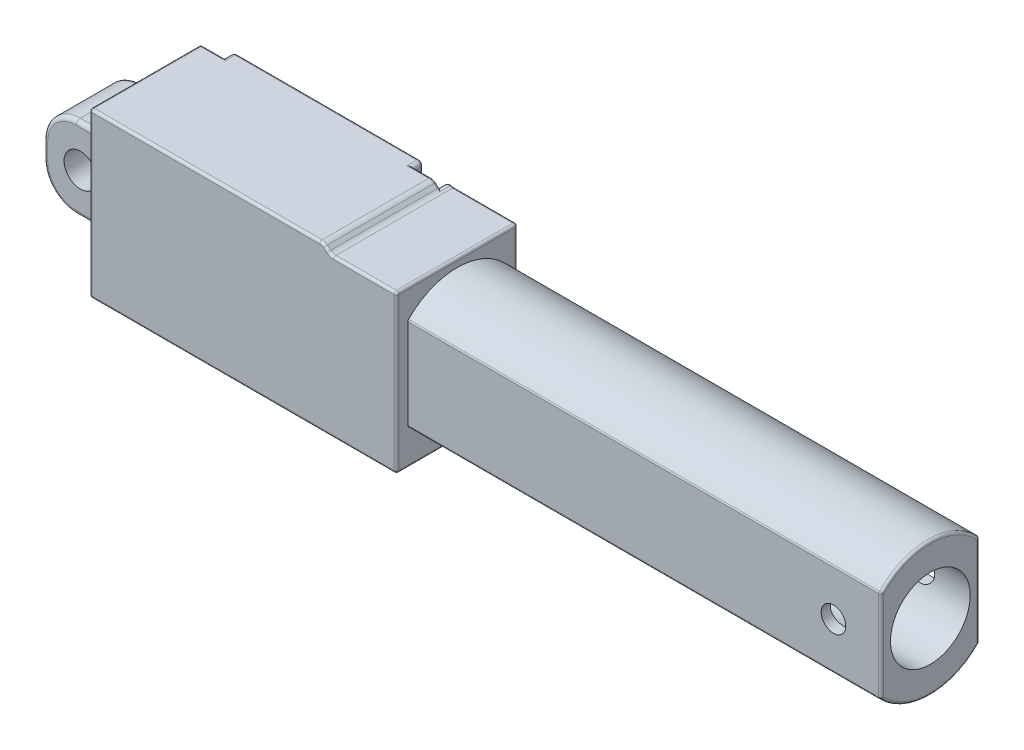
SolidWorks part; units mm, degrees
ref_plane "前视基准面" through (0, 0, 0) normal (0, 0, 1) x (1, 0, 0)
ref_plane "上视基准面" through (0, 0, 0) normal (0, 1, 0) x (1, 0, 0)
ref_plane "右视基准面" through (0, 0, 0) normal (1, 0, 0) x (0, 0, -1)
ref_plane "基准面4" through (0, 0, -7.4) normal (0, 0, -1) x (-1, 0, 0)
sketch "草图1" plane through (0, 0, -7.4) normal (0, 0, -1) x (-1, 0, 0)
  line L0 (47.5729, 10.2265) -> (10.0729, 9.8993)
  line L1 (10.0729, 9.8993) -> (10.0729, -10)
  line L2 (10.0729, -10) -> (47.5729, -10)
  line L3 (47.5729, -10) -> (47.5729, 10.2265)
extrude "凸台-拉伸1" add sketch "草图1" against normal blind 14.8
sketch "草图2" plane through (0, 0, 7.4) normal (0, 0, 1) x (1, 0, 0)
  line L0 (-18.1173, 9.2) -> (-10.0729, 9.2)
  line L1 (-10.0729, 9.2) -> (-10.0729, 9.8993)
  line L2 (-10.0729, 9.8993) -> (-19.0542, 9.9776)
  line L3 (-19.0542, 9.9776) -> (-18.1173, 9.2)
extrude "切除-拉伸1" cut sketch "草图2" against normal through all
sketch "草图3" plane through (0, 0, -7.4) normal (0, 0, -1) x (-1, 0, 0)
  line L0 (19.0542, 9.9776) -> (18.2138, 9.2801)
  line L1 (18.7423, 8.7853) -> (18.7453, 8.4391)
  line L2 (21.6308, 8.4643) -> (21.6174, 10)
  line L3 (21.6174, 10) -> (19.0542, 9.9776)
  arc A0 (18.2138, 9.2801) -> (18.7423, 8.7853) centre (18.2423, 8.7809) cw
  arc A1 (18.7453, 8.4391) -> (21.6308, 8.4643) centre (20.188, 8.4517) ccw
extrude "切除-拉伸2" cut sketch "草图3" against normal blind 1.2
sketch "草图4" plane through (-10.0729, 0, 0) normal (1, 0, 0) x (0, 0, -1)
  line L0 (-6, -5.5893) -> (-6, 5.5893)
  line L1 (6, 5.5893) -> (6, -5.5893)
  arc A0 (6, -5.5893) -> (-6, -5.5893) centre (0, 0) cw
  arc A1 (-6, 5.5893) -> (6, 5.5893) centre (0, 0) cw
extrude "凸台-拉伸2" add sketch "草图4" along normal blind 57.8
sketch "草图5" plane through (-47.5729, 0, 0) normal (-1, 0, 0) x (0, 0, 1)
  line L0 (-4, 4.5) -> (4, 4.5)
  line L1 (4, 4.5) -> (4, -5.5)
  line L2 (4, -5.5) -> (-4, -5.5)
  line L3 (-4, -5.5) -> (-4, 4.5)
extrude "凸台-拉伸3" add sketch "草图5" along normal blind 9
sketch "草图6" plane through (0, 0, -7.4) normal (0, 0, -1) x (-1, 0, 0)
  line L0 (21.827, -10) -> (21.827, -7.952)
  line L1 (18.2413, -7.952) -> (18.2413, -10)
  line L2 (18.2413, -10) -> (21.827, -10)
  arc A0 (21.827, -7.952) -> (18.2413, -7.952) centre (20.0342, -7.952) ccw
extrude "切除-拉伸3" cut sketch "草图6" against normal blind 1.2
sketch "草图7" plane through (0, -10, 0) normal (0, -1, 0) x (1, 0, 0)
  line L0 (-43.5934, -7.4) -> (-43.5934, -6.2)
  line L1 (-43.5934, -6.2) -> (-47.5729, -6.2)
  line L2 (-47.5729, -6.2) -> (-47.5729, -7.4)
  line L3 (-47.5729, -7.4) -> (-43.5934, -7.4)
extrude "切除-拉伸4" cut sketch "草图7" against normal blind 4.4912
sketch "草图8" plane through (-47.5729, 0, 0) normal (-1, 0, 0) x (0, 0, 1)
  line L0 (4.5, 5.2446) -> (-5, 5.2446)
  line L1 (-5, 5.2446) -> (-5, 7.7446)
  line L2 (-5, 7.7446) -> (4.5, 7.7446)
  line L3 (4.5, 7.7446) -> (4.5, 5.2446)
extrude "凸台-拉伸4" add sketch "草图8" along normal blind 1.2
draft "拔模1" type of draft neutral plane draft angle 0.5 faces to draft 1 face at (-29.4148, 10.068, -2.0667) neutral plane through (-21.6308, 8.4643, -6.2) neutral plane normal (1, -0.0087, 0) reverse direction yes parameters "D1"=0.5
draft "拔模2" type of draft neutral plane draft angle 7.063 faces to draft 1 face at (-45.5832, -5.5088, -6.8) neutral plane through (-47.5729, -10, 7.4) neutral plane normal (-1, 0, 0) parameters "D1"=7.063
draft "拔模3" type of draft neutral plane draft angle 7.85 faces to draft 1 face at (-43.5934, -8.0009, -6.8) neutral plane through (-10.0729, -10, 7.4) neutral plane normal (0, -1, 0) parameters "D1"=7.85
hole_wizard "Ø4.0 (4) 直径孔1" positions "草图10" profile "草图9" hole size "Ø4.0" standard "ANSI Metric"
sketch "草图10" plane through (0, 0, 4) normal (0, 0, 1) x (1, 0, 0)
  point P0 (-52.0729, -0.5)
sketch "草图9" plane through (-52.0729, -0.5, 4) normal (1, 0, 0) x (0, -1, 0)
  line L0 (0, 0) -> (0, 11.4)
  line L1 (0, 11.4) -> (2, 11.4)
  line L2 (2, 11.4) -> (2, 0)
  line L5 (2, 0) -> (0, 0)
  line L11 (0, -6.35) -> (0, 107.95) construction
  dimension "通孔孔直径" = 4
  dimension "通孔孔深度" = 11.4
hole_wizard "Ø4.3 (4.3) 直径孔1" positions "草图12" profile "草图11" hole size "Ø4.3" standard "ANSI Metric"
sketch "草图12" plane through (0, 0, -7.4) normal (0, 0, -1) x (-1, 0, 0)
  point P0 (46.95, 9.45)
sketch "草图11" plane through (-46.95, 9.45, -7.4) normal (1, 0, 0) x (0, 1, 0)
  line L0 (0, 0) -> (0, 1.2)
  line L1 (0, 1.2) -> (2.15, 1.2)
  line L2 (2.15, 1.2) -> (2.15, 0)
  line L5 (2.15, 0) -> (0, 0)
  line L10 (0, 1.2) -> (-2.15, 1.2) construction
  line L11 (0, -6.35) -> (0, 107.95) construction
  dimension "孔直径" = 4.3
  dimension "孔深度" = 1.2
  dimension "导头角度" = 180
hole_wizard "Ø1.0 (1) 直径孔1" positions "草图14" profile "草图13" hole size "Ø1.0" standard "ANSI Metric"
sketch "草图14" plane through (0, 0, -6.2) normal (0, 0, -1) x (-1, 0, 0)
  point P0 (20.1, -7.95)
  point P1 (46.1, 8.8)
  point P2 (20.1, 8.8)
  point P3 (46.1, -7.95)
sketch "草图13" plane through (-20.1, -7.95, -6.2) normal (1, 0, 0) x (0, 1, 0)
  line L0 (0, 0) -> (0, 6)
  line L1 (0, 6) -> (0.5, 6)
  line L2 (0.5, 6) -> (0.5, 0)
  line L5 (0.5, 0) -> (0, 0)
  line L10 (0, 6) -> (-0.5, 6) construction
  line L11 (0, -6.35) -> (0, 107.95) construction
  dimension "孔直径" = 1
  dimension "孔深度" = 6
  dimension "导头角度" = 180
hole_wizard "M8 间隙孔1" positions "草图16" profile "草图15" hole size "M8" standard "ANSI Metric"
sketch "草图16" plane through (47.7271, 0, 0) normal (1, 0, 0) x (0, 0, -1)
  point P0 (0, 0)
sketch "草图15" plane through (47.7271, 0, 0) normal (0, 1, 0) x (0, 0, -1)
  line L0 (0, 0) -> (0, 55)
  line L1 (0, 55) -> (4.8688, 55)
  line L2 (4.8688, 55) -> (4.8688, 0)
  line L5 (4.8688, 0) -> (0, 0)
  line L10 (0, 55) -> (-4.8688, 55) construction
  line L11 (0, -6.35) -> (0, 107.95) construction
  dimension "孔直径" = 9.7377
  dimension "孔深度" = 55
  dimension "导头角度" = 180
hole_wizard "Ø3.0 (3) 直径孔1" positions "草图18" profile "草图17" hole size "Ø3.0" standard "ANSI Metric"
sketch "草图18" plane through (0, 0, -6) normal (0, 0, -1) x (-1, 0, 0)
  point P0 (-41.9, 0)
sketch "草图17" plane through (41.9, 0, -6) normal (1, 0, 0) x (0, 1, 0)
  line L0 (0, 0) -> (0, 13.368)
  line L1 (0, 13.368) -> (1.5, 13.368)
  line L2 (1.5, 13.368) -> (1.5, 0)
  line L5 (1.5, 0) -> (0, 0)
  line L10 (0, 13.368) -> (-1.5, 13.368) construction
  line L11 (0, -6.35) -> (0, 107.95) construction
  dimension "孔直径" = 3
  dimension "孔深度" = 13.368
  dimension "导头角度" = 180
fillet "圆角1" radius 4 2 edges at (-56.5729, -5.5, 0) (-56.5729, 4.5, 0) tangent propagation no
fillet "圆角2" radius 0.5 21 edges at (-48.1729, 5.2446, -5) (-50.0729, -5.5, -4) (-50.0729, 4.5, -4) (-55.4014, -4.3284, -4) (-55.4014, 3.3284, -4) (-56.5729, -0.5, -4) (-50.0729, -5.5, 4) (-55.4014, -4.3284, 4) (-50.0729, 4.5, 4) (-56.5729, -0.5, 4) (-55.4014, 3.3284, 4) (-47.5729, -5.5088, -6.8) (-43.5934, -10, -6.8) (-21.6174, 10, -6.8) (-18.2413, -10, -6.8) (-44.8715, 10, -6.8) (-48.1729, 5.2446, 4.5) (-48.1729, 7.7446, -5) (-21.827, -10, -6.8) (-48.1729, 7.7446, 4.5) (-47.5729, 7.3922, -6.8) tangent propagation no
fillet "圆角3" radius 1 2 edges at (-19.0812, 10, 0.6) (-18.1173, 9.2, 0) tangent propagation no
fillet "圆角4" radius 2.1138 1 edges at (-44.1542, -5.9324, -6.8) tangent propagation no
fillet "圆角5" radius 0.3 78 edges at (-47.5729, 7.5982, -4.8536) (-47.5729, 7.7446, -0.25) (-47.5729, 6.4946, -5) (-47.5729, 7.5982, 4.3536) (-47.5729, 5.3911, -4.8536) (-47.5729, 6.4946, 4.5) (-47.5729, 5.2446, -0.25) (-47.5729, 5.3911, 4.3536) (-45.9367, 10, -6.2) (-47.5729, 8.4014, -6.2) (-47.5729, -7.5335, -6.2) (-45.3653, -10, -6.2) (-47.5729, 10, 0.6) (-13.9146, 9.2, -7.4) (-17.9206, 9.2136, -7.4) (-18.5312, 9.189, -7.4) (-18.7438, 8.6122, -7.4) (-20.2006, 7.009, -7.4) (-21.6263, 8.98, -7.4) (-21.7667, 9.852, -7.4) (-33.2111, 10, -7.4) (-44.6573, 9.8502, -7.4) (-45.4508, 7.9089, -7.4) (-47.4182, 7.1645, -7.4) (-47.5729, 0.868, -7.4) (-47.4476, -5.398, -7.4) (-46.4504, -5.6479, -7.4) (-44.5419, -6.3255, -7.4) (-13.9071, -10, -7.4) (-43.7926, -8.555, -7.4) (-18.0949, -9.8536, -7.4) (-43.4861, -9.8769, -7.4) (-18.2413, -8.726, -7.4) (-32.7423, -10, -7.4) (-20.0342, -6.1591, -7.4) (-21.9734, -9.8536, -7.4) (-21.827, -8.726, -7.4) (-10.0729, -0.4, -7.4) (-47.5729, 0, 7.4) (-47.5729, -10, 0.6) (-33.5075, 10, 7.4) (-19.1026, 9.9406, 7.4) (-13.9146, 9.2, 7.4) (-18.5992, 9.6, 7.4) (-18.0958, 9.2594, 7.4) (-10.0729, -10, 0) (-10.0729, 9.2, 0) (-10.0729, -0.4, 7.4) (-28.8229, -10, 7.4) (-47.5729, -5.5, 0) (-47.5729, -5.3536, 3.8536) (-47.5729, -5.3536, -3.8536) (-47.5729, -0.5, 4) (-47.5729, -0.5, -4) (-47.5729, 4.3536, 3.8536) (-47.5729, 4.3536, -3.8536) (-47.5729, 4.5, 0) (18.8271, -5.5893, -6) (47.7271, 0, -6) (18.8271, 5.5893, -6) (47.7271, -8.2, 0) (18.8271, -5.5893, 6) (47.7271, 8.2, 0) (47.7271, 0, 6) (18.8271, 5.5893, 6) (-48.7729, 6.4946, -5) (-48.7729, 5.3911, -4.8536) (-48.7729, 7.5982, -4.8536) (-48.7729, 5.2446, -0.25) (-48.7729, 7.7446, -0.25) (-48.7729, 5.3911, 4.3536) (-48.7729, 7.5982, 4.3536) (-48.7729, 6.4946, 4.5) (-18.2457, 9.3279, -6.2) (-18.5992, 9.6, -6.2) (-20.7819, 10, -6.2) (-19.1026, 9.9406, -6.2) (-20.0342, -10, -6.2) tangent propagation no
